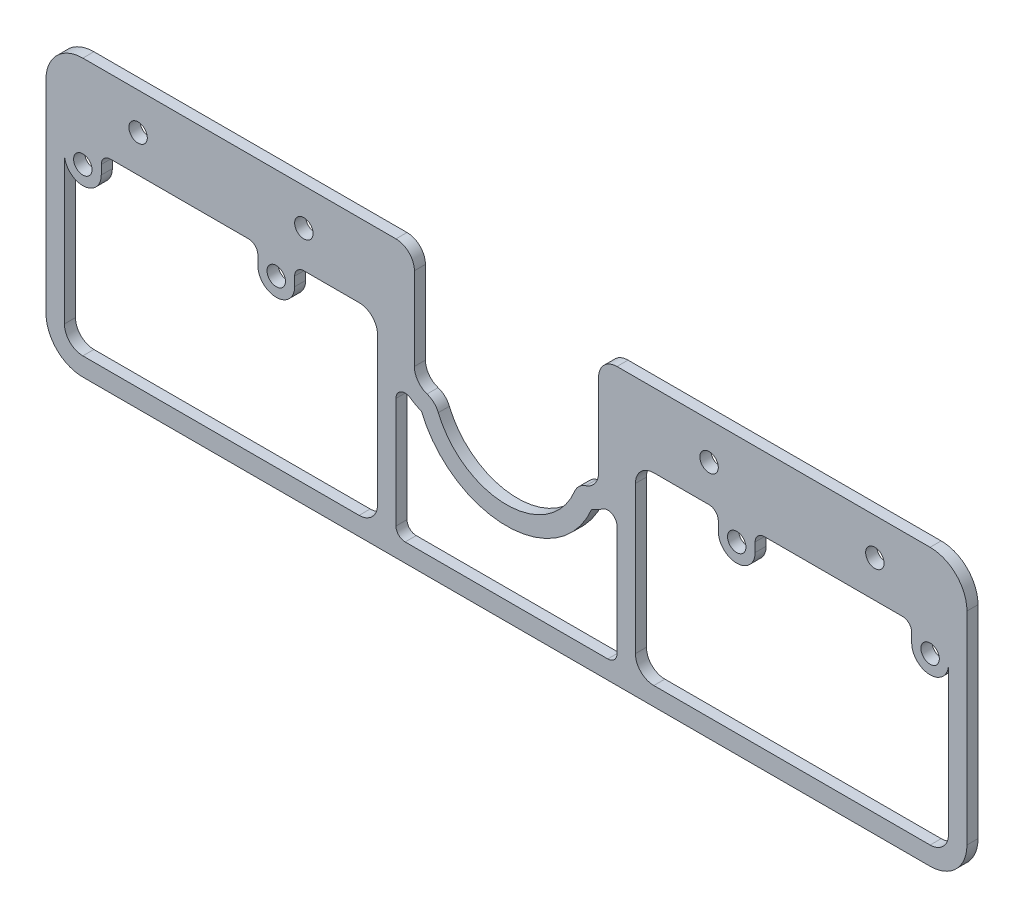
SolidWorks part; units mm, degrees
ref_plane "Front Plane" through (0, 0, 0) normal (0, 0, 1) x (1, 0, 0)
ref_plane "Top Plane" through (0, 0, 0) normal (0, 1, 0) x (1, 0, 0)
ref_plane "Right Plane" through (0, 0, 0) normal (1, 0, 0) x (0, 0, -1)
sketch "Sketch1" plane through (0, 0, 0) normal (0, 0, 1) x (1, 0, 0)
  line L0 (-40, 20) -> (-40, 55) construction
  line L4 (-250, -55) -> (-250, 3.1783)
  line L8 (-50, 75) -> (-230, 75) construction
  line L17 (0, -20) -> (0, -40)
  line L25 (0, -65) -> (0, -75)
  line L26 (0, 75) -> (0, -75) construction
  line L27 (-50, 95) -> (50, 95) construction
  line L34 (0, -75) -> (-230, -75)
  line L156 (-50, 75) -> (-230, 75) construction
  line L161 (0, -40) -> (0, -65)
  line L165 (-164.3309, 75) -> (-60, 75)
  line L167 (-230, 75) -> (-220, 75)
  line L171 (-250, 3.1783) -> (-250, 55)
  line L172 (-220, 75) -> (-164.3309, 75)
  line L173 (-50, 65) -> (-50, 20)
  arc A0 (-40, 20) -> (0, -20) centre (0, 20) ccw construction
  circle A1 centre (0, 20) radius 30 construction
  arc A4 (-230, -75) -> (-250, -55) centre (-230, -55) cw
  arc A5 (-250, 55) -> (-230, 75) centre (-230, 55) cw
  arc A124 (0, -20) -> (-37, 4.8013) centre (0, 20) cw
  arc A125 (-60, 75) -> (-50, 65) centre (-60, 65) cw
  arc A126 (-43.125, 10.5008) -> (-50, 20) centre (-40, 20) cw
  arc A127 (-37, 4.8013) -> (-43.125, 10.5008) centre (-46.25, 1.0016) ccw
  point P0 (0, 0)
  point P10 (-50, 10)
  point P11 (0, 50)
  point P30 (-40, 75)
  point P45 (0, -30)
  point P74 (0, 95)
  dimension "D3" = 80
  dimension "D4" = 60
  dimension "D6" = 55
  dimension "D7" = 75
  dimension "D10" = 10
  dimension "D11" = 20
  dimension "D8" = 10
  dimension "D5" = 10
  dimension "D9" = 20
  dimension "D13" = 210
  dimension "D16" = 100
  dimension "D17" = 20
  dimension "D26" = 250
extrude "Boss-Extrude1" add sketch "Sketch1" along normal blind 6
mirror "Mirror1" about plane through (0, -20, 6) normal (-1, 0, 0) of "Boss-Extrude1"
sketch "Sketch3" plane through (0, 0, 6) normal (0, 0, 1) x (1, 0, 0)
  line L3 (50, 20) -> (50, 65) construction
  line L4 (50, 20) -> (50, 65) construction
  line L7 (-60, 75) -> (-230, 75) construction
  line L8 (-250, 55) -> (-250, -55) construction
  line L9 (250, 55) -> (250, -55) construction
  circle A2 centre (110, 55) radius 5
  circle A3 centre (200, 55) radius 5
  circle A4 centre (-200, 55) radius 5
  circle A5 centre (-110, 55) radius 5
  dimension "D3" = 10
  dimension "D4" = 10
  dimension "D5" = 10
  dimension "D6" = 10
  dimension "D8" = 20
  dimension "D12" = 50
  dimension "D2" = 140
  dimension "D7" = 20
  dimension "D9" = 50
  dimension "D10" = 140
extrude "Cut-Extrude1" cut sketch "Sketch3" against normal through all contours A2 | A3 | A5 | A4 region at (110, 55, 6) region at (200, 55, 6) region at (-110, 55, 6)
sketch "Sketch4" plane through (0, 0, 6) normal (0, 0, 1) x (1, 0, 0)
  line L0 (-230, -75) -> (230, -75) construction
  line L1 (-70, 25) -> (-70, -55)
  line L2 (-50, 20) -> (-50, 65) construction
  line L3 (-60, 75) -> (-230, 75) construction
  line L7 (-240, -55) -> (-240, 25)
  line L8 (-250, 55) -> (-250, -55) construction
  line L9 (-210, -65) -> (-190, -65)
  line L10 (-115, 25) -> (-115, 30)
  line L11 (-110, 35) -> (-80, 35)
  line L12 (-220, 25) -> (-220, 30)
  line L13 (-215, 35) -> (-140, 35)
  line L14 (-135, 30) -> (-135, 25)
  line L15 (-230, -65) -> (-210, -65)
  line L16 (-110, -65) -> (-90, -65)
  line L17 (0, 0) -> (0, -75) construction
  line L18 (-190, -65) -> (-110, -65)
  line L19 (90, -65) -> (80, -65)
  line L20 (190, -65) -> (110, -65)
  line L21 (-90, -65) -> (-80, -65)
  line L22 (110, -65) -> (90, -65)
  line L23 (230, -65) -> (210, -65)
  line L24 (230, 25) -> (125, 25) construction
  line L30 (221.3397, 20) -> (133.6603, 20)
  line L32 (110, 35) -> (80, 35)
  line L33 (115, 25) -> (115, 30)
  line L35 (210, -65) -> (190, -65)
  line L36 (240, -55) -> (240, 25)
  line L37 (70, 25) -> (70, -55)
  line L38 (125, 35) -> (230, 35)
  line L39 (230, 20) -> (125, 20) construction
  circle A0 centre (-230, 25) radius 5
  circle A3 centre (-125, 25) radius 5
  arc A6 (-230, -65) -> (-240, -55) centre (-230, -55) cw
  arc A8 (-222.2775, 18.6468) -> (-231.6408, 15.1355) centre (-230, 25) ccw
  arc A9 (-127.2754, 15.2623) -> (-127.1893, 15.2426) centre (-125, 25) ccw
  arc A12 (-110, 35) -> (-115, 30) centre (-110, 30) ccw
  arc A13 (-140, 35) -> (-135, 30) centre (-140, 30) cw
  arc A14 (-215, 35) -> (-220, 30) centre (-215, 30) ccw
  arc A15 (-70, -55) -> (-80, -65) centre (-80, -55) cw
  arc A16 (-70, 25) -> (-80, 35) centre (-80, 25) ccw
  arc A17 (-117.6445, 18.2253) -> (-134.5708, 22.1017) centre (-125, 25) ccw
  arc A19 (-231.6408, 15.1355) -> (-222.2775, 18.6468) centre (-230, 25) ccw
  arc A20 (-134.5708, 22.1017) -> (-117.3815, 18.5225) centre (-125, 25) ccw
  arc A21 (133.6603, 20) -> (117.3815, 18.5225) centre (125, 25) cw
  arc A22 (231.6408, 15.1355) -> (222.2775, 18.6468) centre (230, 25) cw
  arc A23 (117.6445, 18.2253) -> (125, 35) centre (125, 25) cw
  arc A24 (70, 25) -> (80, 35) centre (80, 25) cw
  arc A25 (70, -55) -> (80, -65) centre (80, -55) ccw
  arc A26 (230, 35) -> (231.6408, 15.1355) centre (230, 25) cw
  arc A28 (110, 35) -> (115, 30) centre (110, 30) cw
  arc A29 (127.2754, 15.2623) -> (127.1893, 15.2426) centre (125, 25) cw
  arc A30 (222.2775, 18.6468) -> (221.3397, 20) centre (230, 25) cw
  arc A31 (230, -65) -> (240, -55) centre (230, -55) ccw
  circle A32 centre (125, 25) radius 5
  circle A33 centre (230, 25) radius 5
  point P0 (0, -75)
  dimension "D1" = 10
  dimension "D13" = 10
  dimension "D14" = 20
  dimension "D10" = 5
  dimension "D15" = 5
  dimension "D17" = 10
  dimension "D2" = 230
  dimension "D4" = 5
  dimension "D5" = 125
  dimension "D8" = 50
  dimension "D9" = 10
  dimension "D11" = 20
  dimension "D12" = 80
  dimension "D16" = 80
extrude "Cut-Extrude2" cut sketch "Sketch4" against normal through all contours A20 A17 L14 A13 L13 A14 L12 A8 A19 L7 A6 L15 L9 L18 L16 L21 A15 L1 A16 L11 A12 L10 A9 | A0 | A3 region at (-154.1168, -16.7892, 6) region at (-230, 25, 6) region at (-125, 25, 6)
sketch "Sketch8" plane through (0, 0, 6) normal (0, 0, 1) x (1, 0, 0)
  line L0 (-60, 0) -> (-60, -65)
  line L2 (-60, -65) -> (60, -65)
  line L3 (60, -65) -> (60, 0)
  line L4 (-230, -65) -> (-80, -65) construction
  arc A0 (43.125, 10.5008) -> (50, 20) centre (40, 20) ccw construction
  arc A1 (43.125, 10.5008) -> (37, 4.8013) centre (46.25, 1.0016) ccw construction
  arc A2 (-37, 4.8013) -> (-43.125, 10.5008) centre (-46.25, 1.0016) ccw construction
  arc A3 (-50, 20) -> (-43.125, 10.5008) centre (-40, 20) ccw construction
  arc A4 (-37, 4.8013) -> (37, 4.8013) centre (0, 20) ccw construction
  arc A5 (43.125, 10.5008) -> (50, 20) centre (40, 20) ccw construction
  arc A6 (43.125, 10.5008) -> (37, 4.8013) centre (46.25, 1.0016) ccw construction
  arc A7 (-37, 4.8013) -> (-43.125, 10.5008) centre (-46.25, 1.0016) ccw construction
  arc A8 (-50, 20) -> (-43.125, 10.5008) centre (-40, 20) ccw construction
  arc A9 (-37, 4.8013) -> (37, 4.8013) centre (0, 20) ccw construction
  arc A10 (-52, 4) -> (-46.25, 1.0016) centre (-40, 20) ccw
  arc A11 (-46.25, 1.0016) -> (-46.25, 1.0016) centre (-46.25, 1.0016) ccw
  arc A12 (-46.25, 1.0016) -> (46.25, 1.0016) centre (0, 20) ccw
  arc A13 (46.25, 1.0016) -> (46.25, 1.0016) centre (46.25, 1.0016) ccw
  arc A14 (46.25, 1.0016) -> (52, 4) centre (40, 20) ccw
  arc A15 (46.25, 1.0016) -> (60, 20) centre (40, 20) ccw construction
  arc A16 (60, 0) -> (52, 4) centre (55, 0) ccw
  arc A17 (-60, 20) -> (-46.25, 1.0016) centre (-40, 20) ccw construction
  arc A18 (-60, 0) -> (-52, 4) centre (-55, 0) cw
  dimension "D2" = 5
  dimension "D1" = 10
extrude "Cut-Extrude5" cut sketch "Sketch8" against normal through all
fillet "Fillet5" radius 5 1 edges at (-60, -65, 3)
fillet "Fillet6" radius 5 1 edges at (60, -65, 3)
mirror "Mirror2" about plane through (0, 0, 0) normal (1, 0, 0) of "Cut-Extrude2"
